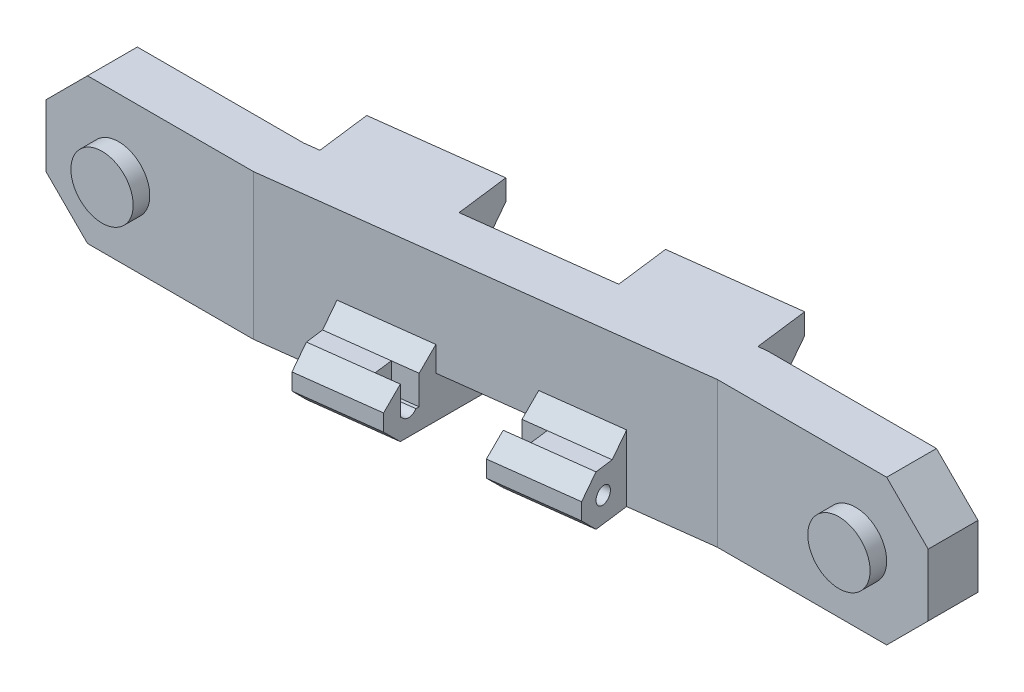
SolidWorks part; units mm, degrees
note: The reader was unsure of these and kept them because the rebuilt part matched: shared geometry of "Sketch1<8>", "Sketch1<10>".
ref_plane "Front Plane" through (0, 0, 0) normal (0, 0, 1) x (1, 0, 0)
ref_plane "Top Plane" through (0, 0, 0) normal (0, 1, 0) x (1, 0, 0)
ref_plane "Right Plane" through (0, 0, 0) normal (1, 0, 0) x (0, 0, -1)
sketch "Sketch1" plane through (0, 0, 0) normal (0, 1, 0) x (1, 0, 0)
  line L0 (-20, -1.25) -> (-9.9216, -1.25) construction
  line L5 (-9.9216, -1.25) -> (9.9216, 1.25) construction
  line L6 (9.9216, 1.25) -> (20, 1.25) construction
  line L7 (-20, -2.45) -> (-20, -0.05)
  line L8 (20, 2.45) -> (20, 0.05)
  line L9 (-20, -0.05) -> (-10, -0.05)
  line L11 (-10, -0.05) -> (9.8431, 2.45)
  line L15 (9.8431, 2.45) -> (20, 2.45)
  line L16 (-20, -2.45) -> (-10, -2.45)
  line L17 (-10, -2.45) -> (9.8431, 0.05)
  line L18 (9.8431, 0.05) -> (20, 0.05)
  line L19 (-10, 2.45) -> (-9.69, -0.0109)
  line L20 (-10, -2.45) -> (-9.6875, -4.9304)
  line L21 (9.8431, 4.95) -> (9.8431, 2.45) construction
  line L22 (-12, -2.45) -> (-12, -4.95)
  line L23 (12, 0.05) -> (12, -2.45)
  line L24 (-12, -4.95) -> (-9.8431, -4.95)
  line L25 (-9.8431, -4.95) -> (10, -2.45)
  line L26 (10, -2.45) -> (12, -2.45)
  line L29 (-12, -0.05) -> (-12, 2.45)
  line L30 (-12, 2.45) -> (-10, 2.45)
  line L33 (9.8431, 4.95) -> (12, 4.95)
  line L34 (12, 4.95) -> (12, 2.45)
  line L35 (-10, 2.45) -> (9.8431, 4.95)
  line L40 (-6.1182, -4.4807) -> (-6.1182, 0.4391) construction
  line L41 (5.9613, -0.4391) -> (5.9613, 4.4609) construction
  line L42 (-10, -0.05) -> (-10, 2.45) construction
  line L43 (-2.51, 3.3936) -> (-2.2, 0.9327)
  line L44 (2.2, 3.9871) -> (2.51, 1.5261)
  line L45 (9.8431, 2.45) -> (9.5331, 4.9109)
  line L46 (10, -2.45) -> (9.6875, 0.0304)
  line L47 (2.2, -0.9129) -> (2.5125, -3.3933)
  line L48 (-6.1182, -4.4807) -> (-6.4307, -2.0003)
  line L49 (-9.845, 1.2195) -> (-6.4716, 1.6445) construction
  line L50 (6.3148, 3.2555) -> (9.6881, 3.6805) construction
  line L51 (5.9613, -0.4391) -> (6.2738, -2.9195)
  line L54 (-20, -2.45) -> (-20, -15.0342) construction
  line L55 (-2.2, -3.9871) -> (-2.5125, -1.5067)
  line L56 (-6.3166, 0.4141) -> (-6.6267, 2.875)
  line L57 (-2.2, 3.4327) -> (-2.2, -3.9871)
  line L58 (2.2, 3.9871) -> (2.2, -3.4327)
  line L60 (5.9613, 4.4609) -> (6.2714, 2) construction
  line L61 (-10, -0.05) -> (-10, -2.45) construction
  line L65 (-6.4282, 2.9) -> (-6.1182, 0.4391) construction
  line L67 (6.1598, 4.4859) -> (6.4698, 2.025)
  line L69 (-20, -15.0342) -> (20, -15.0342) construction
  line L70 (20, -15.0342) -> (20, 0.05) construction
  line L73 (-6.2744, -3.2405) -> (-9.8438, -3.6902) construction
  line L75 (0, -15.0342) -> (0, 0) construction
  line L76 (-9.8438, -3.6902) -> (-12, -3.7) construction
  line L77 (9.8438, -1.2098) -> (12, -1.2) construction
  point P7 (-20, -1.25)
  point P11 (20, 1.25)
  point P26 (0, 0)
  dimension "D1" = 2.5
  dimension "D2" = 3.4
  dimension "D3" = 2.4
  dimension "D4" = 2.5
  dimension "D5" = 3.4
  dimension "D6" = 20
  dimension "D7" = 40
  dimension "D8" = 8
  dimension "D9" = 8
  dimension "D10" = 2.5
  dimension "D11" = 0.2
  dimension "D13" = 0.2
  dimension "D14" = 2.2
  dimension "D15" = 2.2
extrude "Boss-Extrude4" add sketch "Sketch1" along normal blind 2.4
extrude "Boss-Extrude5" add sketch "Sketch1<8>" along normal offset from surface (7 mm away) 4.6 contours L57 L11 L9 L7 L16 L17 | L11 L58 L17 L18 L8 L15 | L58 L11 L57 L17 up to face at (-8.1583, 2.4, -1.432) offset beyond the face yes
sketch "Sketch1<8>" plane through (0, 0, 0) normal (0, 1, 0) x (1, 0, 0) same geometry as "Sketch1"
sketch "Sketch2" plane through (0, 0, 2.45) normal (0, 0, 1) x (1, 0, 0)
  line L0 (-20, 7) -> (-13, 0) construction
  line L1 (-20, 7) -> (-13, 7)
  line L2 (-20, 7) -> (-20, 0)
  line L3 (-20, 0) -> (-13, 0)
  line L4 (-13, 7) -> (-13, 0)
  line L5 (-20, 0) -> (-13, 7) construction
  line L6 (-20, 0) -> (-10, 0) construction
  line L21 (-16.5, 5.2321) -> (-18, 4.366) construction
  line L22 (-20, 7) -> (-20, 0) construction
  line L23 (-18, 4.366) -> (-18, 2.634) construction
  line L24 (-18, 2.634) -> (-16.5, 1.7679) construction
  line L26 (-16.5, 1.7679) -> (-15, 2.634) construction
  line L27 (-15, 2.634) -> (-15, 4.366) construction
  line L28 (-20, 7) -> (-10, 7) construction
  line L29 (-15, 4.366) -> (-16.5, 5.2321) construction
  circle A1 centre (-16.5, 3.5) radius 1.5
  dimension "D1" = 3
  dimension "D3" = 0
  dimension "D4" = 0
sketch "Sketch3" plane through (0, 0, -0.05) normal (0, 0, 1) x (1, 0, 0)
  line L0 (13, 0) -> (20, 7) construction
  line L1 (13, 0) -> (20, 0)
  line L2 (13, 0) -> (13, 7)
  line L3 (13, 7) -> (20, 7)
  line L4 (20, 0) -> (20, 7)
  line L5 (13, 7) -> (20, 0) construction
  line L6 (9.8431, 0) -> (20, 0) construction
  line L21 (9.8431, 7) -> (20, 7) construction
  line L22 (20, 7) -> (20, 0) construction
  line L23 (16.5, 5.2321) -> (15, 4.366) construction
  line L24 (15, 4.366) -> (15, 2.634) construction
  line L25 (15, 2.634) -> (16.5, 1.7679) construction
  line L26 (16.5, 1.7679) -> (18, 2.634) construction
  line L27 (18, 2.634) -> (18, 4.366) construction
  line L28 (18, 4.366) -> (16.5, 5.2321) construction
  circle A1 centre (16.5, 3.5) radius 1.5
  dimension "D1" = 3
  dimension "D3" = 0
  dimension "D4" = 0
extrude "Boss-Extrude8" add sketch "Sketch2" along normal blind 0.8
extrude "Boss-Extrude9" add sketch "Sketch3" along normal blind 0.8
sketch "Sketch4" plane through (0, 0, 0.05) normal (0, 0, -1) x (-1, 0, 0)
  line L0 (13, 0) -> (20, 7) construction
  line L1 (20, 7) -> (13, 7)
  line L2 (20, 7) -> (20, 0)
  line L3 (20, 0) -> (13, 0)
  line L4 (13, 7) -> (13, 0)
  line L5 (13, 7) -> (20, 0) construction
  line L6 (20, 7) -> (20, 0) construction
  line L21 (20, 7) -> (10, 7) construction
  line L22 (20, 0) -> (10, 0) construction
  line L23 (16.5, 5.463) -> (14.8, 4.4815) construction
  line L24 (14.8, 4.4815) -> (14.8, 2.5185) construction
  line L25 (14.8, 2.5185) -> (16.5, 1.537) construction
  line L26 (16.5, 1.537) -> (18.2, 2.5185) construction
  line L27 (18.2, 2.5185) -> (18.2, 4.4815) construction
  line L28 (18.2, 4.4815) -> (16.5, 5.463) construction
  circle A1 centre (16.5, 3.5) radius 1.7
  dimension "D2" = 3.4
  dimension "D3" = 0
sketch "Sketch5" plane through (0, 0, -2.45) normal (0, 0, -1) x (-1, 0, 0)
  line L0 (-20, 7) -> (-13, 0) construction
  line L1 (-20, 7) -> (-13, 7)
  line L2 (-20, 7) -> (-20, 0)
  line L3 (-20, 0) -> (-13, 0)
  line L4 (-13, 7) -> (-13, 0)
  line L5 (-20, 0) -> (-13, 7) construction
  line L6 (-20, 7) -> (-20, 0) construction
  line L21 (-9.8431, 7) -> (-20, 7) construction
  line L22 (-9.8431, 0) -> (-20, 0) construction
  line L23 (-16.5, 5.463) -> (-18.2, 4.4815) construction
  line L24 (-18.2, 4.4815) -> (-18.2, 2.5185) construction
  line L25 (-18.2, 2.5185) -> (-16.5, 1.537) construction
  line L26 (-16.5, 1.537) -> (-14.8, 2.5185) construction
  line L27 (-14.8, 2.5185) -> (-14.8, 4.4815) construction
  line L28 (-14.8, 4.4815) -> (-16.5, 5.463) construction
  circle A1 centre (-16.5, 3.5) radius 1.7
  dimension "D2" = 3.4
  dimension "D3" = 0
extrude "Cut-Extrude3" cut sketch "Sketch4" against normal blind 1.2
extrude "Cut-Extrude4" cut sketch "Sketch5" against normal blind 1.2
chamfer "Chamfer4" distance 2 angle 45 4 edges at (20, 7, -1.25) (20, 0, -1.25) (-20, 7, 1.25) (-20, 0, 1.25)
sketch "Sketch8" plane through (9.9932, 0, -1.259) normal (0.9922, 0, -0.125) x (-0.125, 0, -0.9922)
  line L0 (2.4808, 1.2) -> (2.4808, 0) construction
  line L1 (3.6808, 0) -> (1.2808, 0)
  line L2 (3.6808, 0) -> (3.6808, 2.4)
  line L3 (3.6808, 2.4) -> (1.2808, 2.4)
  line L4 (1.2808, 0) -> (1.2808, 2.4)
  line L5 (2.4808, 1.2) -> (3.6808, 1.2) construction
  line L6 (3.6808, 2.4) -> (3.6808, 0) construction
  line L7 (-2.4808, 1.2) -> (-3.6808, 1.2) construction
  line L8 (2.0808, 1.4309) -> (2.0808, 1.7381)
  line L9 (2.0808, 1.7381) -> (2.8808, 1.7381)
  line L10 (2.4808, 1.6619) -> (2.0808, 1.4309) construction
  line L11 (2.0808, 1.4309) -> (2.0808, 0.9691) construction
  line L12 (2.0808, 0.9691) -> (2.4808, 0.7381) construction
  line L13 (2.4808, 0.7381) -> (2.8808, 0.9691) construction
  line L14 (2.8808, 0.9691) -> (2.8808, 1.4309) construction
  line L15 (2.8808, 1.4309) -> (2.4808, 1.6619) construction
  line L16 (-2.4808, 1.2) -> (-2.4808, 0) construction
  line L17 (-2.8808, 1.7381) -> (-2.0808, 1.7381)
  line L19 (-3.6808, 0) -> (-1.2808, 0)
  line L20 (-3.6808, 0) -> (-3.6808, 2.4)
  line L21 (-3.6808, 2.4) -> (-1.2808, 2.4)
  line L22 (-1.2808, 0) -> (-1.2808, 2.4)
  line L25 (-3.6808, 2.4) -> (-3.6808, 0) construction
  line L26 (2.8808, 1.7381) -> (2.8808, 1.4309)
  line L27 (-2.4808, 1.6619) -> (-2.8808, 1.4309) construction
  line L28 (-2.8808, 1.4309) -> (-2.8808, 0.9691) construction
  line L29 (-2.8808, 0.9691) -> (-2.4808, 0.7381) construction
  line L30 (-2.4808, 0.7381) -> (-2.0808, 0.9691) construction
  line L31 (-2.0808, 0.9691) -> (-2.0808, 1.4309) construction
  line L32 (-2.0808, 1.4309) -> (-2.4808, 1.6619) construction
  line L33 (-2.8808, 1.4309) -> (-2.8808, 1.7381)
  line L35 (-2.0808, 1.4309) -> (-2.0808, 1.7381)
  line L36 (-3.6808, 2.4) -> (-1.1808, 2.4) construction
  line L38 (3.6808, 2.4) -> (3.6808, 0) construction
  line L39 (1.2004, 0) -> (3.6808, 0) construction
  line L40 (1.2004, 2.4) -> (3.6808, 2.4) construction
  circle A0 centre (2.4808, 1.2) radius 0.4
  circle A1 centre (-2.4808, 1.2) radius 0.4
  point P0 (1.8887, 1.2)
  point P12 (-1.8887, 1.2)
  dimension "D2" = 1
  dimension "D1" = 0.8
  dimension "D3" = 1
  dimension "D4" = 1.2
extrude "Cut-Extrude7" cut sketch "Sketch8" against normal up to surface (19.6875 mm away) up to face at (-9.845, 1.2, -1.2195)
extrude "Cut-Extrude10" cut sketch "Sketch1<10>" along normal offset from surface (2 mm away) 2 contours L58 L11 L57 L17 | L58 L35 L57 L11 | L58 L17 L57 L25 up to face at (-0.4825, 0, 0.1082)
sketch "Sketch1<10>" plane through (0, 0, 0) normal (0, 1, 0) x (1, 0, 0) same geometry as "Sketch1"
chamfer "Chamfer6" distance 0.8 angle 45 12 edges at (4.2369, 0, 3.1761) (4.2369, 2.4, 3.1761) (7.8464, 0, -4.6984) (7.8464, 2.4, -4.6984) (-4.1591, 0, 4.2339) (-4.1591, 2.4, 4.2339) (4.0807, 2.4, 0.676) (-4.3153, 2.4, 1.7338) (-8.3133, 0, -2.6625) (-8.3133, 2.4, -2.6625) (8.1565, 2.4, -2.2375) (-8.0033, 2.4, -0.2016)
chamfer "Chamfer7" [suppressed] distance 0.8 angle 45
sketch "Sketch9" plane through (0, 2.4, 0) normal (0, 1, 0) x (1, 0, 0)
  line L0 (-9.9, 1.6563) -> (-9.79, 0.7828)
  line L1 (-9.79, 0.7828) -> (-8.5994, 0.9328)
  line L3 (-8.5994, 0.9328) -> (-8.7094, 1.8063)
  line L5 (-8.7094, 1.8063) -> (-9.9, 1.6563)
  line L6 (-2.2, -2.2736) -> (-3.3906, -2.4236)
  line L7 (2.2, -2.6264) -> (6.1738, -2.1257) construction
  line L8 (-3.3906, -2.4236) -> (-3.2781, -3.3166)
  line L9 (6.0613, -1.2328) -> (2.2, -1.7193) construction
  line L10 (-3.2781, -3.3166) -> (-2.0875, -3.1666)
  line L11 (-2.0875, -3.1666) -> (-2.2, -2.2736)
  line L12 (2.2, -2.6264) -> (2.0875, -1.7334)
  line L13 (2.0875, -1.7334) -> (3.2781, -1.5834)
  line L15 (3.2781, -1.5834) -> (3.3906, -2.4764)
  line L17 (3.3906, -2.4764) -> (2.2, -2.6264)
  line L18 (9.6331, 4.1172) -> (8.4425, 3.9672)
  line L20 (8.4425, 3.9672) -> (8.5525, 3.0937)
  line L22 (8.5525, 3.0937) -> (9.7431, 3.2437)
  line L23 (9.7431, 3.2437) -> (9.6331, 4.1172)
  line L27 (-6.2182, -3.687) -> (-2.2, -3.1807) construction
  line L31 (6.3698, 2.8187) -> (9.7431, 3.2437) construction
  line L32 (9.7431, 3.2437) -> (9.6331, 4.1172) construction
  line L33 (9.6331, 4.1172) -> (6.2598, 3.6922) construction
  line L34 (-9.79, 0.7828) -> (-6.4166, 1.2078) construction
  line L35 (-9.9, 1.6563) -> (-9.79, 0.7828) construction
  line L36 (-6.5267, 2.0813) -> (-9.9, 1.6563) construction
  dimension "D4" = 1.2
extrude "Cut-Extrude11" cut sketch "Sketch9" against normal blind 1.4 and the other way blind 10
sketch "Sketch10" plane through (0, 7, 0) normal (0, 1, 0) x (1, 0, 0)
  line L10 (-10, -0.05) -> (9.8431, 2.45) construction
  line L12 (-6.4166, 1.2078) -> (-6.5267, 2.0813) construction
  line L18 (3.1683, 4.2296) -> (3.4933, 1.65)
  line L21 (-9.2931, 0.0391) -> (-9.6181, 2.6187)
  line L22 (-9.6181, 2.6187) -> (-3.6651, 3.3687)
  line L23 (-3.6651, 3.3687) -> (-3.3401, 0.7891)
  line L24 (-3.3401, 0.7891) -> (-9.2931, 0.0391)
  line L30 (3.4933, 1.65) -> (9.4463, 2.4)
  line L31 (9.4463, 2.4) -> (9.1213, 4.9796)
  line L32 (9.1213, 4.9796) -> (3.1683, 4.2296)
  line L33 (6.2598, 3.6922) -> (6.3698, 2.8187) construction
  dimension "D1" = 6
  dimension "D2" = 2.6
  dimension "D3" = 3
  dimension "D4" = 3
extrude "Boss-Extrude10" add sketch "Sketch10" against normal offset from surface (3.6 mm away) 3.6 up to face at (-0.0392, 7, 0)
chamfer "Chamfer8" distance 2.6 angle 45 2 edges at (-6.6416, 3.4, -2.9937) (6.1448, 3.4, -4.6046)
sketch "Sketch11" plane through (0, 0, 0) normal (0, 0, 1) x (1, 0, 0)
  line L0 (10.059, 31.6467) -> (36.3088, 31.6467) construction
  line L1 (45.8151, 31.6467) -> (70.8151, 31.6467) construction
  line L2 (42.0816, 62.6523) -> (43.1395, 56.6523)
  line L3 (42.0816, 62.6523) -> (39.8977, 68.6523)
  line L4 (39.8977, 68.6523) -> (36.4336, 74.6523)
  line L5 (43.1395, 56.6523) -> (43.1395, 48.6523)
  line L6 (35.3395, 48.6523) -> (35.3395, 55.9699)
  line L7 (35.3395, 55.9699) -> (34.5186, 60.6258)
  line L8 (34.5186, 60.6258) -> (32.8015, 65.3433)
  line L9 (32.8015, 65.3433) -> (27.427, 74.6523)
  line L10 (35.3395, 48.6523) -> (43.1395, 48.6523)
  line L11 (27.427, 74.6523) -> (36.4336, 74.6523)
  circle A0 centre (10.059, 31.6467) radius 25
  circle A1 centre (70.8151, 31.6467) radius 25
  point P6 (38.1657, 71.6523)
  dimension "D1" = 50
  dimension "D2" = 6
  dimension "D3" = 8
  dimension "D4" = 170
  dimension "D5" = 6
  dimension "D6" = 6
  dimension "D7" = 170
  dimension "D8" = 170
  dimension "D9" = 7.8
  dimension "D10" = 7.8
  dimension "D11" = 7.8
  dimension "D12" = 7.8
  dimension "D13" = 7.3176
  dimension "D14" = 4.6559
  dimension "D15" = 4.7175
  dimension "D16" = 9.309
  dimension "D17" = 0.821
  dimension "D18" = 1.717
  dimension "D19" = 5.3746
